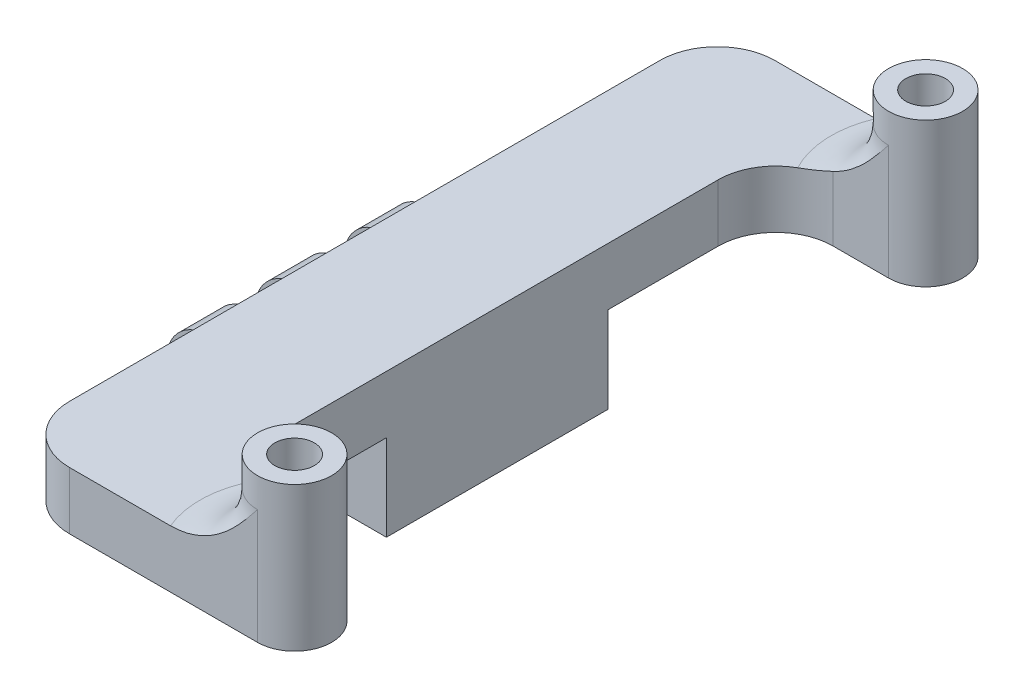
SolidWorks part; units mm, degrees
ref_plane "Front Plane" through (0, 0, 0) normal (0, 0, 1) x (1, 0, 0)
ref_plane "Top Plane" through (0, 0, 0) normal (0, 1, 0) x (1, 0, 0)
ref_plane "Right Plane" through (0, 0, 0) normal (1, 0, 0) x (0, 0, -1)
sketch "Sketch2" plane through (0, 0, 0) normal (0, 0, 1) x (1, 0, 0)
  line L0 (0, 3) -> (9.22, 3)
  line L1 (9.22, 3) -> (9.22, -3)
  line L2 (9.22, -3) -> (0, -3)
  line L3 (0, -3) -> (0, 3)
  point P4 (0, 0)
  dimension "D2" = 6
  dimension "D3" = 9.22
extrude "Boss-Extrude1" add sketch "Sketch2" along normal mid plane 15.43
sketch "Sketch4" plane through (0, 0, 7.715) normal (0, 0, 1) x (1, 0, 0)
  line L0 (0, 3) -> (-3.1, 3)
  line L1 (0, -3) -> (-3.1, -3)
  line L2 (0, 3) -> (0, -3)
  arc A0 (-3.1, 3) -> (-3.1, -3) centre (-3.1, 0) ccw
  circle A1 centre (-3.1, 0) radius 1.375
  dimension "D1" = 6
  dimension "D3" = 2.75
  dimension "D2" = 3.1
extrude "Boss-Extrude2" add sketch "Sketch4" against normal blind 3.086
pattern_linear "LPattern1" count 3 spacing 6.172 along (0, 0, -1) of "Boss-Extrude2"
sketch "Sketch6" plane through (0, 3, 0) normal (0, 1, 0) x (1, 0, 0)
  line L3 (0, 24.535) -> (0, -24.535)
  line L4 (0, -24.535) -> (17.07, -24.535)
  line L6 (17.07, -19.375) -> (9.22, -19.375)
  line L7 (9.22, -19.375) -> (9.22, 19.375)
  line L8 (9.22, 19.375) -> (17.07, 19.375)
  line L10 (17.07, 24.535) -> (0, 24.535)
  arc A0 (17.07, 19.375) -> (17.07, 24.535) centre (17.07, 21.955) ccw
  arc A1 (17.07, -24.535) -> (17.07, -19.375) centre (17.07, -21.955) ccw
  dimension "D5" = 2.58
  dimension "D1" = 9.22
  dimension "D2" = 7.85
  dimension "D3" = 43.91
extrude "Boss-Extrude3" add sketch "Sketch6" along normal blind 4
sketch "Sketch7" plane through (0, 7, 0) normal (0, 1, 0) x (1, 0, 0)
  circle A0 centre (17.07, 21.955) radius 2.58
  circle A1 centre (17.07, -21.955) radius 2.58
  arc A6 (17.07, 19.375) -> (17.07, 24.535) centre (17.07, 21.955) ccw construction
  arc A7 (17.07, -24.535) -> (17.07, -19.375) centre (17.07, -21.955) ccw construction
  dimension "D1" = 2.58
extrude "Boss-Extrude4" add sketch "Sketch7" along normal offset from surface (6.05 mm away) 16.05 up to face at (-0.0133, -3, 0)
sketch "Sketch8" plane through (0, 13.05, 0) normal (0, 1, 0) x (1, 0, 0)
  circle A0 centre (17.07, 21.955) radius 1.375
  circle A1 centre (17.07, -21.955) radius 1.375
  circle A2 centre (17.07, -21.955) radius 2.58 construction
  circle A4 centre (17.07, 21.955) radius 2.58 construction
  dimension "D1" = 2.75
extrude "Cut-Extrude1" cut sketch "Sketch8" against normal through all
fillet "Fillet1" radius 4 4 edges at (14.49, 7, 21.955) (14.49, 7, -21.955) (0, 5, -24.535) (0, 5, 24.535)
fillet "Fillet2" radius 4 2 edges at (9.22, 5, -19.375) (9.22, 5, 19.375)
